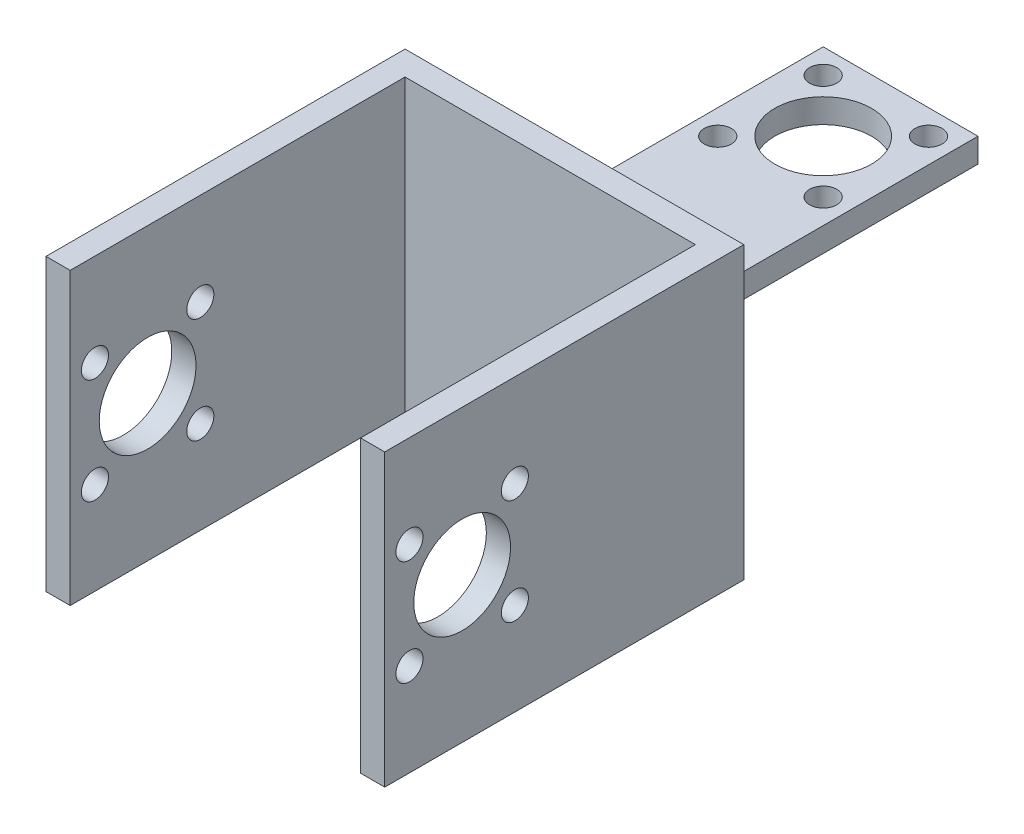
SolidWorks part; units mm, degrees
ref_plane "Front Plane" through (0, 0, 0) normal (0, 0, 1) x (1, 0, 0)
ref_plane "Top Plane" through (0, 0, 0) normal (0, 1, 0) x (1, 0, 0)
ref_plane "Right Plane" through (0, 0, 0) normal (1, 0, 0) x (0, 0, -1)
sketch "Sketch1" plane through (0, 0, 0) normal (0, 1, 0) x (1, 0, 0)
  line L0 (0, 0) -> (-20.32, 0)
  line L1 (-20.32, 0) -> (-20.32, -43.561)
  line L2 (0, 0) -> (0, -43.561)
  line L3 (-20.32, -43.561) -> (-31.623, -43.561)
  line L4 (-31.623, -43.561) -> (-31.623, -90.678)
  line L5 (-31.623, -90.678) -> (-28.448, -90.678)
  line L6 (-28.448, -90.678) -> (-28.448, -46.736)
  line L7 (-28.448, -46.736) -> (9.652, -46.736)
  line L8 (9.652, -46.736) -> (9.652, -90.678)
  line L9 (0, -43.561) -> (12.827, -43.561)
  line L10 (9.652, -90.678) -> (12.827, -90.678)
  line L11 (12.827, -43.561) -> (12.827, -90.678)
  dimension "D1" = 20.32
  dimension "D2" = 46.736
  dimension "D3" = 43.561
  dimension "D4" = 38.1
  dimension "D5" = 3.175
  dimension "D6" = 3.175
  dimension "D8" = 90.678
  dimension "D9" = 90.678
  dimension "D10" = 43.561
extrude "Boss-Extrude1" add sketch "Sketch1" along normal mid plane 38.1
sketch "Sketch3" plane through (0, -19.05, 0) normal (0, -1, 0) x (1, 0, 0)
  line L0 (0, 43.561) -> (-20.32, 43.561)
  line L1 (-20.32, 43.561) -> (-20.32, 0)
  line L2 (-20.32, 0) -> (0, 0)
  line L3 (0, 0) -> (0, 43.561)
extrude "Cut-Extrude1" cut sketch "Sketch3" against normal blind 19.05
sketch "Sketch4" plane through (0, 19.05, 0) normal (0, 1, 0) x (1, 0, 0)
  line L0 (-20.32, -43.561) -> (0, -43.561)
  line L1 (0, -43.561) -> (0, 0)
  line L2 (0, 0) -> (-20.32, 0)
  line L3 (-20.32, 0) -> (-20.32, -43.561)
extrude "Cut-Extrude2" cut sketch "Sketch4" against normal blind 15.875
sketch "Sketch6" plane through (0, 3.175, 0) normal (0, 1, 0) x (1, 0, 0)
  line L0 (-10.16, 0) -> (-10.16, -20.32) construction
  line L1 (0, 0) -> (-20.32, 0) construction
  line L2 (-10.16, -10.16) -> (-17.0748, -17.0748) construction
  line L3 (-10.16, -10.16) -> (-17.0748, -3.2452) construction
  line L4 (-10.16, -10.16) -> (-3.2452, -3.2452) construction
  line L5 (-10.16, -10.16) -> (-3.2452, -17.0748) construction
  circle A0 centre (-10.16, -10.16) radius 6.35
  circle A1 centre (-17.0748, -17.0748) radius 1.778
  circle A2 centre (-17.0748, -3.2452) radius 1.778
  circle A3 centre (-3.2452, -3.2452) radius 1.778
  circle A4 centre (-3.2452, -17.0748) radius 1.778
  point P14 (0, 0)
extrude "Cut-Extrude3" cut sketch "Sketch6" against normal up to next
sketch "Sketch9" plane through (12.827, 0, 0) normal (1, 0, 0) x (0, 0, -1)
  line L0 (-90.678, 0) -> (-70.358, 0) construction
  line L1 (-90.678, 19.05) -> (-90.678, -19.05) construction
  line L2 (-80.518, 0) -> (-87.4328, 6.9148) construction
  line L3 (-80.518, 0) -> (-87.4328, -6.9148) construction
  line L4 (-80.518, 0) -> (-73.6032, -6.9148) construction
  line L5 (-80.518, 0) -> (-73.6032, 6.9148) construction
  circle A0 centre (-80.518, 0) radius 6.35
  circle A1 centre (-87.4328, 6.9148) radius 1.778
  circle A2 centre (-73.6032, 6.9148) radius 1.778
  circle A3 centre (-73.6032, -6.9148) radius 1.778
  circle A4 centre (-87.4328, -6.9148) radius 1.778
extrude "Cut-Extrude6" cut sketch "Sketch9" against normal up to next
sketch "Sketch10" plane through (-31.623, 0, 0) normal (-1, 0, 0) x (0, 0, 1)
  line L0 (90.678, 0) -> (70.358, 0) construction
  line L1 (90.678, 19.05) -> (90.678, -19.05) construction
  line L2 (80.518, 0) -> (87.4328, 6.9148) construction
  line L3 (80.518, 0) -> (87.4328, -6.9148) construction
  line L4 (80.518, 0) -> (73.6032, -6.9148) construction
  line L5 (80.518, 0) -> (73.6032, 6.9148) construction
  circle A0 centre (80.518, 0) radius 6.35
  circle A1 centre (73.6032, 6.9148) radius 1.778
  circle A2 centre (87.4328, 6.9148) radius 1.778
  circle A3 centre (87.4328, -6.9148) radius 1.778
  circle A4 centre (73.6032, -6.9148) radius 1.778
extrude "Cut-Extrude7" cut sketch "Sketch10" against normal up to next
